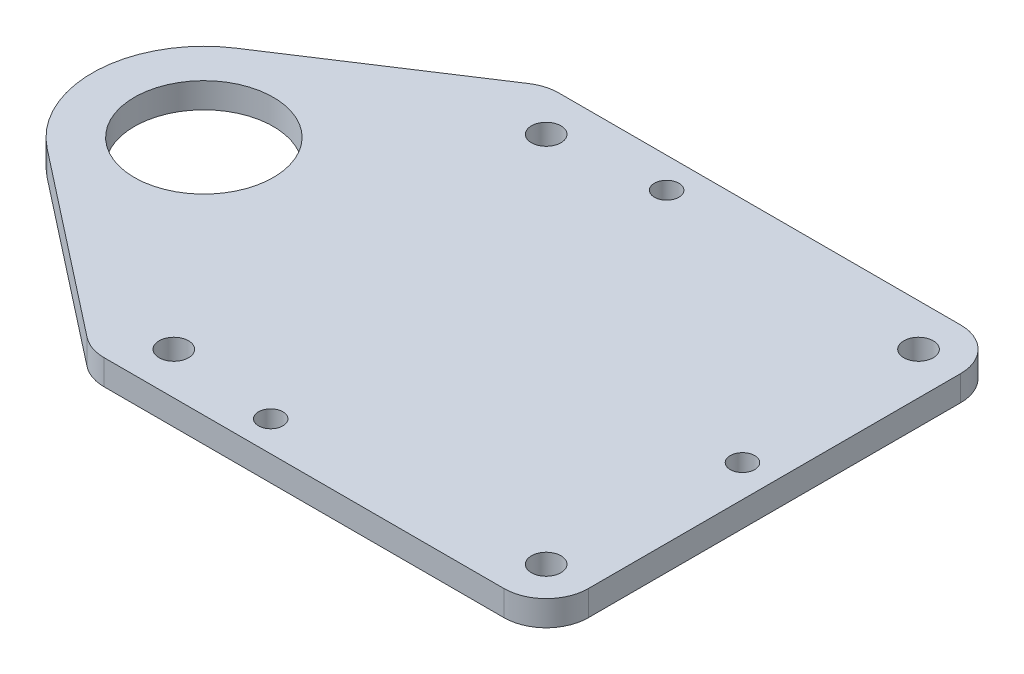
SolidWorks part; units mm, degrees
ref_plane "Front Plane" through (0, 0, 0) normal (0, 0, 1) x (1, 0, 0)
ref_plane "Top Plane" through (0, 0, 0) normal (0, 1, 0) x (1, 0, 0)
ref_plane "Right Plane" through (0, 0, 0) normal (1, 0, 0) x (0, 0, -1)
sketch "Sketch1" plane through (0, 0, 0) normal (0, 1, 0) x (1, 0, 0)
  line L0 (17.9, 50.6) -> (17.9, 3.6) construction
  line L1 (0, 0) -> (54.2, 0)
  line L2 (0, 0) -> (0, 54.2)
  line L3 (0, 54.2) -> (54.2, 54.2)
  line L4 (54.2, 0) -> (54.2, 54.2)
  line L5 (17.9, 27.1) -> (50.4, 27.1) construction
  line L6 (0, 54.2) -> (17.9, 50.6) construction
  line L7 (0, 0) -> (17.9, 3.6) construction
  line L8 (5, 49.2) -> (0, 54.2) construction
  line L9 (5, 49.2) -> (49.2, 49.2) construction
  line L10 (5, 49.2) -> (5, 5) construction
  line L11 (5, 5) -> (49.2, 5) construction
  line L12 (49.2, 49.2) -> (49.2, 5) construction
  line L13 (49.2, 49.2) -> (54.2, 54.2) construction
  line L14 (49.2, 5) -> (54.2, 0) construction
  line L15 (5, 5) -> (0, 0) construction
  line L16 (0, 0) -> (-23.1656, 18.1279)
  line L18 (0, 54.2) -> (-22.2506, 39.6528)
  circle A0 centre (17.9, 50.6) radius 1.45
  circle A1 centre (17.9, 3.6) radius 1.45
  circle A2 centre (50.4, 27.1) radius 1.45
  circle A3 centre (5, 49.2) radius 1.75
  circle A4 centre (49.2, 49.2) radius 1.75
  circle A5 centre (49.2, 5) radius 1.75
  circle A6 centre (5, 5) radius 1.75
  circle A7 centre (-15, 28.5627) radius 8.25
  circle A8 centre (-15, 28.5627) radius 13.25
  point P25 (0, 0)
  dimension "D1" = 47
  dimension "D4" = 2.9
  dimension "D7" = 3.5
  dimension "D9" = 16.5
  dimension "D10" = 26.5
  dimension "D2" = 32.5
  dimension "D3" = 54.2
  dimension "D5" = 54.2
  dimension "D6" = 3.8
  dimension "D8" = 5
  dimension "D11" = 15
extrude "Boss-Extrude1" add sketch "Sketch1" along normal blind 3 contours L1 L4 L3 L2 A6 A5 A4 A3 A2 A1 A0 | A8 L16 L2 L18 | A8 A7 region at (27.0888, 0, -27.1) region at (-11.2196, 0, -9.5281) region at (-27.8636, 0, -29.1095)
fillet "Fillet1" radius 5 4 edges at (54.2, 1.5, -54.2) (54.2, 1.5, 0) (0, 1.5, 0) (0, 1.5, -54.2)
